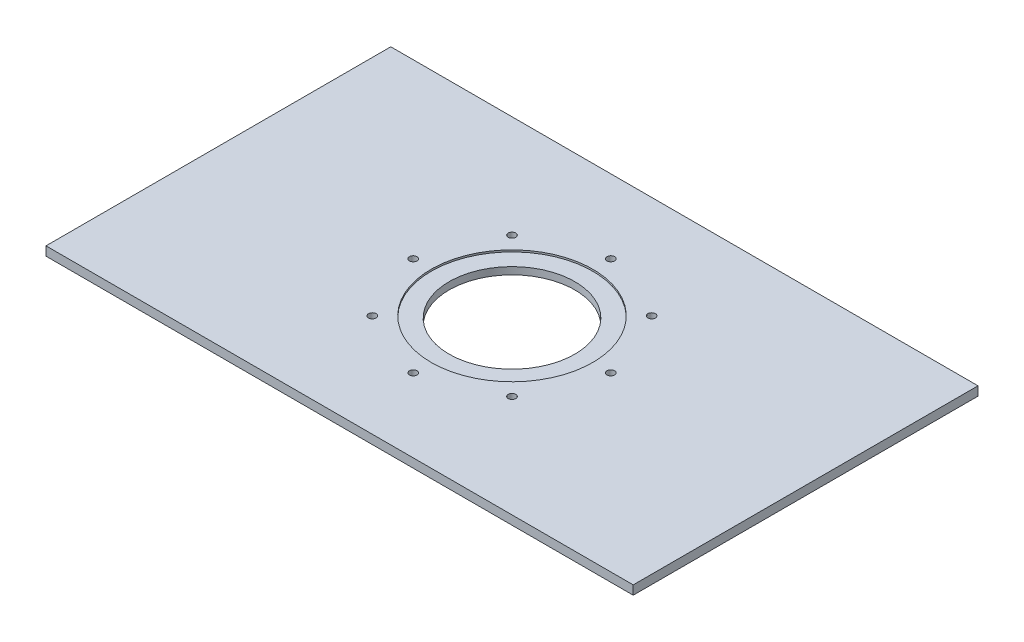
SolidWorks part; units mm, degrees
material "6061-T6 (SS)"
ref_plane "Front Plane" through (0, 0, 0) normal (0, 0, 1) x (1, 0, 0)
ref_plane "Top Plane" through (0, 0, 0) normal (0, 1, 0) x (1, 0, 0)
ref_plane "Right Plane" through (0, 0, 0) normal (1, 0, 0) x (0, 0, -1)
sketch "Sketch1" plane through (0, 0, 0) normal (0, 1, 0) x (1, 0, 0)
  line L1 (-163.5, -96) -> (163.5, -96)
  line L2 (-163.5, -96) -> (-163.5, 96)
  line L3 (-163.5, 96) -> (163.5, 96)
  line L4 (163.5, -96) -> (163.5, 96)
  line L5 (-163.5, -96) -> (163.5, 96) construction
  line L6 (-163.5, 96) -> (163.5, -96) construction
  point P0 (0, 0)
  dimension "D1" = 192
  dimension "D2" = 327
extrude "Boss-Extrude1" add sketch "Sketch1" along normal blind 5
sketch "Sketch2" plane through (0, 5, 0) normal (0, 1, 0) x (1, 0, 0)
  circle A0 centre (0, 0) radius 35
  dimension "D1" = 70
extrude "Cut-Extrude1" cut sketch "Sketch2" against normal through all
sketch "Sketch3" plane through (0, 5, 0) normal (0, 1, 0) x (1, 0, 0)
  circle A0 centre (0, 0) radius 45
  dimension "D1" = 90
extrude "Cut-Extrude2" cut sketch "Sketch3" against normal blind 1
sketch "Sketch6" plane through (0, 5, 0) normal (0, 1, 0) x (1, 0, 0)
  circle A0 centre (0, 0) radius 55
  point P4 (-55, 0)
  point P10 (-38.8909, 38.8909)
  point P11 (0, 55)
  point P12 (38.8909, 38.8909)
  point P13 (55, 0)
  point P14 (38.8909, -38.8909)
  point P15 (0, -55)
  point P16 (-38.8909, -38.8909)
  dimension "D1" = 110
  dimension "D2" = 8
hole_wizard "Tap Drill for M4 Helicoil1" positions "Sketch6" profile "Sketch5" hole size "M4x0.7" standard "DIN" end condition through all
sketch "Sketch5" plane through (-38.8909, 5, 38.8909) normal (1, 0, 0) x (0, 0, 1)
  line L0 (0, 0) -> (0, 5)
  line L1 (0, 5) -> (2.1, 5)
  line L2 (2.1, 5) -> (2.1, 0)
  line L5 (2.1, 0) -> (0, 0)
  line L11 (0, -6.35) -> (0, 107.95) construction
  dimension "Thru Hole Dia." = 4.2
  dimension "Thru Hole Depth" = 5
